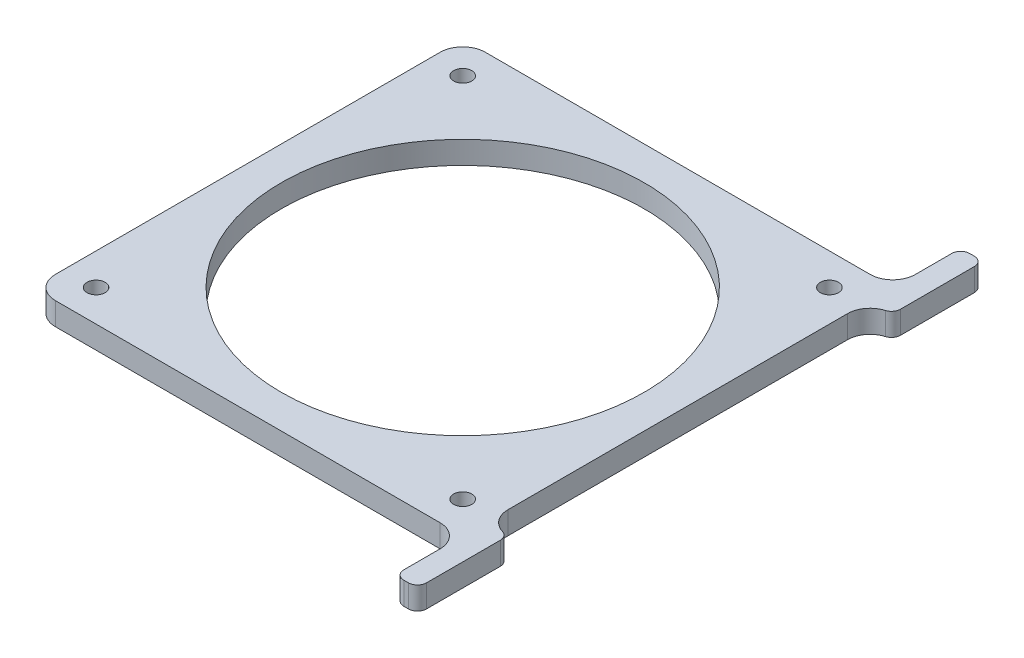
SolidWorks part; units mm, degrees
ref_plane "Front Plane" through (0, 0, 0) normal (0, 0, 1) x (1, 0, 0)
ref_plane "Top Plane" through (0, 0, 0) normal (0, 1, 0) x (1, 0, 0)
ref_plane "Right Plane" through (0, 0, 0) normal (1, 0, 0) x (0, 0, -1)
sketch "Sketch1" plane through (0, 0, 0) normal (0, 1, 0) x (1, 0, 0)
  line L1 (-47.5, -47.5) -> (47.5, -47.5)
  line L2 (-47.5, -47.5) -> (-47.5, 47.5)
  line L3 (-47.5, 47.5) -> (47.5, 47.5)
  line L4 (47.5, -47.5) -> (47.5, 47.5)
  line L5 (-47.5, -47.5) -> (47.5, 47.5) construction
  line L6 (-47.5, 47.5) -> (47.5, -47.5) construction
  line L7 (-40.5, -40.5) -> (40.5, -40.5)
  line L8 (-40.5, -40.5) -> (-40.5, 40.5)
  line L9 (-40.5, 40.5) -> (40.5, 40.5)
  line L10 (40.5, -40.5) -> (40.5, 40.5)
  line L11 (-40.5, -40.5) -> (40.5, 40.5) construction
  line L12 (-40.5, 40.5) -> (40.5, -40.5) construction
  circle A0 centre (0, 0) radius 40.1
  point P0 (0, 0)
  dimension "D3" = 80.2
  dimension "D1" = 95
  dimension "D2" = 95
  dimension "D4" = 81
extrude "Boss-Extrude1" add sketch "Sketch1" along normal blind 5 contours L7 L10 L9 L8 A0 | L1 L4 L3 L2 L10 L7 L8 L9 region at (-46.1565, 0, 0) region at (-40.3854, 0, 0)
hole_wizard "Ø4.0mm Dowel Hole1" positions "Sketch2" profile "Sketch4" hole size "Ø4.0" standard "ANSI Metric" end condition through all
sketch "Sketch2" plane through (0, 0, 0) normal (0, -1, 0) x (-1, 0, 0)
  point P0 (40.5, -40.5)
  point P3 (-40.5, -40.5)
  point P6 (-40.5, 40.5)
  point P9 (40.5, 40.5)
sketch "Sketch4" plane through (-40.5, 0, 40.5) normal (1, 0, 0) x (0, 0, -1)
  line L0 (0, 0) -> (0, 5)
  line L1 (0, 5) -> (2, 5)
  line L2 (2, 5) -> (2, 0)
  line L5 (2, 0) -> (0, 0)
  line L11 (0, -6.35) -> (0, 107.95) construction
  dimension "Thru Hole Dia." = 4
  dimension "Thru Hole Depth" = 5
sketch "Sketch5" plane through (0, 0, 0) normal (0, 1, 0) x (1, 0, 0)
  line L0 (47.5, -47.5) -> (47.5, 47.5) construction
  line L1 (47.5, -42.5) -> (52.5, -42.5)
  line L2 (47.5, -42.5) -> (47.5, -62.5)
  line L3 (47.5, -62.5) -> (52.5, -62.5)
  line L4 (52.5, -42.5) -> (52.5, -62.5)
  line L6 (47.5, 42.5) -> (52.5, 42.5)
  line L7 (47.5, 42.5) -> (47.5, 62.5)
  line L8 (47.5, 62.5) -> (52.5, 62.5)
  line L9 (52.5, 42.5) -> (52.5, 62.5)
  dimension "D1" = 15
  dimension "D2" = 15
  dimension "D3" = 5
  dimension "D4" = 5
  dimension "D5" = 5
  dimension "D6" = 5
extrude "Boss-Extrude2" add sketch "Sketch5" along normal blind 5
fillet "Fillet1" radius 5 6 edges at (-47.5, 2.5, -47.5) (-47.5, 2.5, 47.5) (47.5, 2.5, 47.5) (47.5, 2.5, 42.5) (47.5, 2.5, -42.5) (47.5, 2.5, -47.5)
fillet "Fillet2" radius 2 6 edges at (47.5, 2.5, -62.5) (52.5, 2.5, -62.5) (52.5, 2.5, 62.5) (47.5, 2.5, 62.5) (52.5, 2.5, 42.5) (52.5, 2.5, -42.5)
